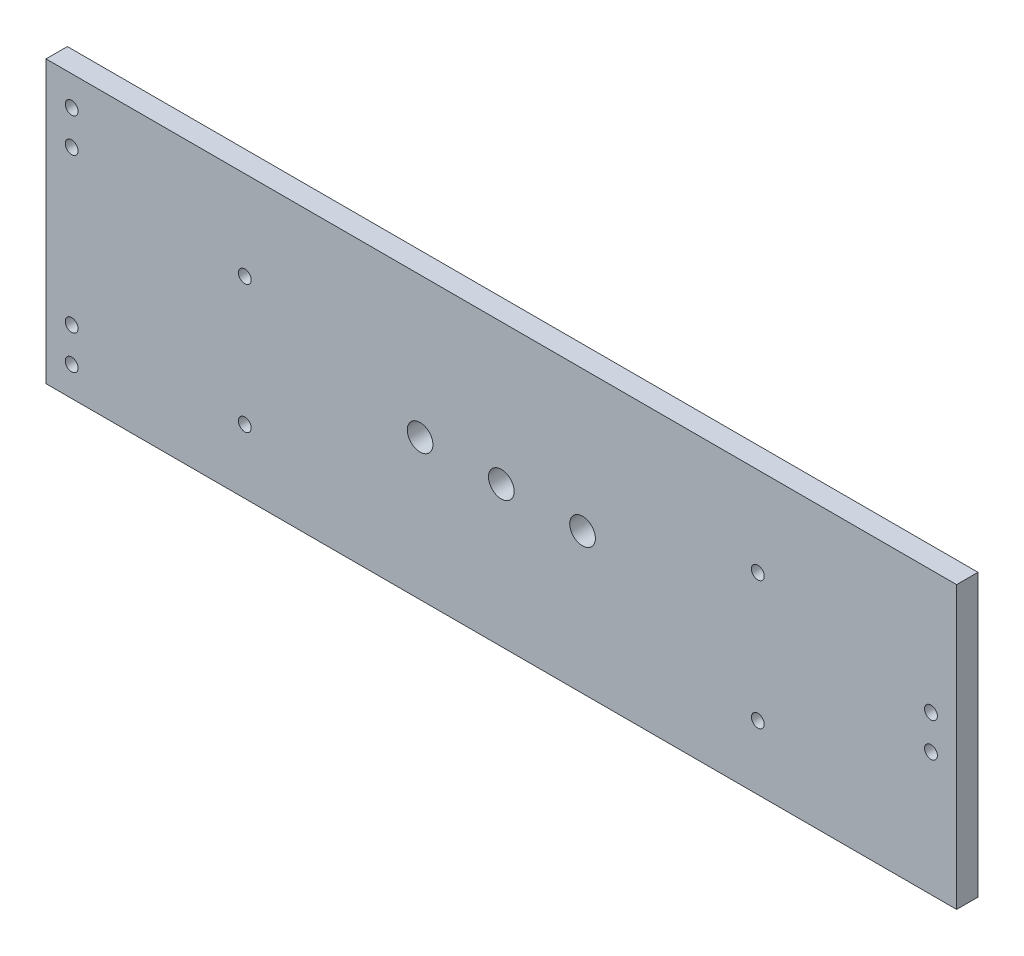
SolidWorks part; units mm, degrees
ref_plane "前视基准面" through (0, 0, 0) normal (0, 0, 1) x (1, 0, 0)
ref_plane "上视基准面" through (0, 0, 0) normal (0, 1, 0) x (1, 0, 0)
ref_plane "右视基准面" through (0, 0, 0) normal (1, 0, 0) x (0, 0, -1)
sketch "草图3" plane through (0, 0, 0) normal (0, 0, 1) x (1, 0, 0)
  line L1 (106.5, -32.9) -> (-106.5, -32.9)
  line L2 (106.5, -32.9) -> (106.5, 32.9)
  line L3 (106.5, 32.9) -> (-106.5, 32.9)
  line L4 (-106.5, -32.9) -> (-106.5, 32.9)
  line L5 (106.5, -32.9) -> (-106.5, 32.9) construction
  line L6 (106.5, 32.9) -> (-106.5, -32.9) construction
  line L7 (125, -27.9) -> (40, -27.9) construction
  line L8 (125, -27.9) -> (125, 27.9) construction
  line L9 (125, 27.9) -> (40, 27.9) construction
  line L10 (40, -27.9) -> (40, 27.9) construction
  line L11 (125, -27.9) -> (40, 27.9) construction
  line L12 (125, 27.9) -> (40, -27.9) construction
  line L13 (-30, -3) -> (30, -3) construction
  line L14 (-30, -3) -> (-30, 3) construction
  line L15 (-30, 3) -> (30, 3) construction
  line L16 (30, -3) -> (30, 3) construction
  line L17 (-30, -3) -> (30, 3) construction
  line L18 (-30, 3) -> (30, -3) construction
  circle A4 centre (0, 0) radius 3
  point P0 (0, 0)
  point P6 (82.5, 0)
  point P19 (0, 0)
  dimension "D21" = 6
  dimension "D1" = 213
  dimension "D2" = 55.8
  dimension "D3" = 5
  dimension "D4" = 5
  dimension "D5" = 85
  dimension "D6" = 40
  dimension "D17" = 60
  dimension "D18" = 0
  dimension "D19" = 6
  dimension "D20" = 0
extrude "凸台-拉伸2" add sketch "草图3" along normal blind 5
sketch "草图4" plane through (0, 0, 5) normal (0, 0, 1) x (1, 0, 0)
  line L0 (-106.5, -32.9) -> (106.5, -32.9) construction
  line L3 (0, 32.9) -> (0, -32.9) construction
  line L4 (106.5, 32.9) -> (-106.5, 32.9) construction
  circle A0 centre (60, 12.1) radius 1.5
  circle A1 centre (60, -17.9) radius 1.5
  circle A2 centre (-60, -17.9) radius 1.5
  circle A3 centre (-60, 12.1) radius 1.5
  dimension "D1" = 3
  dimension "D2" = 3
  dimension "D3" = 60
  dimension "D4" = 30
  dimension "D5" = 15
extrude "切除-拉伸1" cut sketch "草图4" against normal blind 5
sketch "草图5" plane through (0, 0, 5) normal (0, 0, 1) x (1, 0, 0)
  line L0 (106.5, 32.9) -> (-106.5, 32.9) construction
  line L1 (-106.5, 32.9) -> (-106.5, -32.9) construction
  line L2 (-100.5, 26) -> (-100.5, 4) construction
  line L3 (-106.5, -32.9) -> (106.5, -32.9) construction
  line L4 (0, 32.9) -> (0, -32.9) construction
  circle A0 centre (-100.5, 26) radius 1.5
  circle A12 centre (-100.5, 18) radius 1.5
  circle A13 centre (-100.5, 4) radius 1.5
  circle A14 centre (-100.5, -4) radius 1.5
  circle A15 centre (-100.5, -18) radius 1.5
  circle A16 centre (-100.5, -26) radius 1.5
  circle A17 centre (100.5, -26) radius 1.5
  circle A18 centre (100.5, -18) radius 1.5
  circle A19 centre (100.5, -4) radius 1.5
  circle A20 centre (100.5, 4) radius 1.5
  circle A21 centre (100.5, 18) radius 1.5
  circle A22 centre (100.5, 26) radius 1.5
  dimension "D1" = 3
  dimension "D4" = 3
  dimension "D2" = 6.9
  dimension "D3" = 6
  dimension "D5" = 8
  dimension "D6" = 3
  dimension "D7" = 22
extrude "切除-拉伸2" cut sketch "草图5" against normal blind 5 contours A0 | A12 | A20 | A19 | A15 | A16 region at (-100.5, 26, 5) region at (-100.5, 18, 5) region at (-100.5, -18, 5) region at (-100.5, -26, 5) region at (100.5, -4, 5) region at (100.5, 4, 5)
sketch "草图6" plane through (0, 0, 5) normal (0, 0, 1) x (1, 0, 0)
  circle A0 centre (19, 0) radius 3
  circle A1 centre (-19, 0) radius 3
  dimension "D3" = 6
  dimension "D4" = 6
  dimension "D1" = 19
  dimension "D2" = 19
extrude "切除-拉伸3" cut sketch "草图6" against normal blind 10
